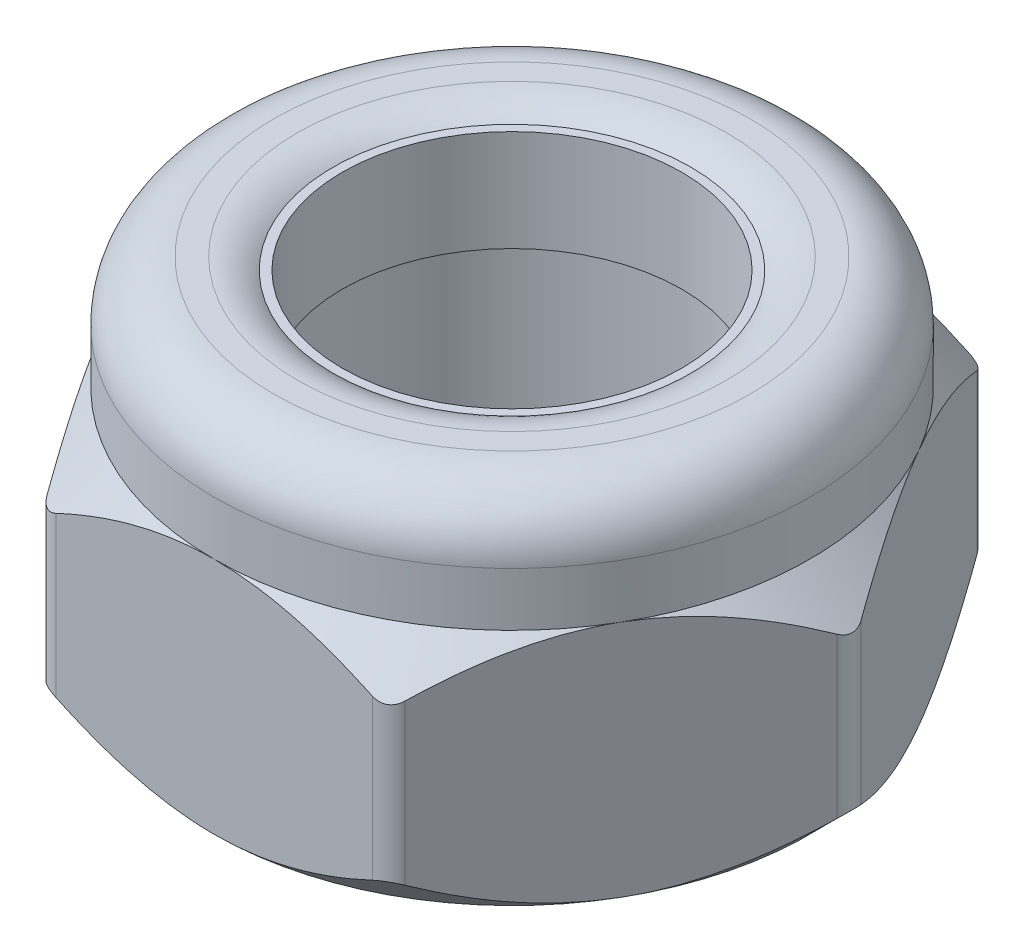
SolidWorks part; units mm, degrees
material "铸造碳钢"
ref_plane "Front" through (0, 0, 0) normal (0, 0, 1) x (1, 0, 0)
ref_plane "Top" through (0, 0, 0) normal (0, 1, 0) x (1, 0, 0)
ref_plane "Right" through (0, 0, 0) normal (1, 0, 0) x (0, 0, -1)
sketch "草图1" plane through (0, 0, 0) normal (0, 1, 0) x (1, 0, 0)
  line L1 (5.7735, 0) -> (2.8868, 5)
  line L2 (2.8868, 5) -> (-2.8868, 5)
  line L3 (-2.8868, 5) -> (-5.7735, 0)
  line L4 (-5.7735, 0) -> (-2.8868, -5)
  line L5 (-2.8868, -5) -> (2.8868, -5)
  line L6 (2.8868, -5) -> (5.7735, 0)
  circle A0 centre (0, 0) radius 5 construction
  dimension "六角对边长" = 10
extrude "凸台-拉伸1" add sketch "草图1" along normal mid plane 4
sketch "草图3" plane through (0, 2, 0) normal (0, 1, 0) x (1, 0, 0)
  circle A0 centre (0, 0) radius 5
  dimension "圆形外直径" = 10
extrude "凸台-拉伸2" add sketch "草图3" along normal blind 1.9
sketch "草图4" plane through (0, 3.9, 0) normal (0, 1, 0) x (1, 0, 0)
  circle A0 centre (0, 0) radius 3
  dimension "螺母内径" = 6
extrude "切除-拉伸1" cut sketch "草图4" against normal through all
sketch "草图5" plane through (0, 3.9, 0) normal (0, 1, 0) x (1, 0, 0)
  circle A0 centre (0, 0) radius 3
  circle A1 centre (0, 0) radius 2.85
  dimension "橡胶内径" = 5.7
  dimension "橡皮圈外直径" = 6
extrude "凸台-拉伸3" add sketch "草图5" against normal up to surface (1.9 mm away) from offset 0.2 up to face at (-5.0345, 2, 0) offset against normal yes
fillet "圆角1" radius 1 2 edges at (0, 3.9, 3) (0, 3.9, 5)
sketch "草图6" plane through (0, 0, 0) normal (0, 0, 1) x (1, 0, 0)
  line L0 (0, -1000) -> (0, 49000) construction
  line L1 (-1000, 0) -> (49000, 0) construction
  line L2 (-5.7735, 2) -> (-5.7735, 1.2265)
  line L3 (-5.7735, 1.2265) -> (-5, 2)
  line L4 (-5, 2) -> (-5.7735, 2)
  line L5 (0, 2) -> (-4.3301, 2) construction
  line L6 (-5.7735, 2) -> (-5.7735, -2) construction
  line L7 (-5, -998.4247) -> (-5, 49001.5753) construction
  line L8 (-5, 2.9) -> (-5, 2) construction
  line L9 (-5.7735, -2) -> (-5.7735, -1.2265)
  line L10 (-5.7735, -1.2265) -> (-5, -2)
  line L11 (-5, -2) -> (-5.7735, -2)
  dimension "D1" = 45
revolve "切除-旋转1" cut sketch "草图6" angle 360 about L0
fillet "圆角3" radius 0.4 6 edges at (-5.7735, 0, 0) (-2.8868, 0, -5) (2.8868, 0, -5) (5.7735, 0, 0) (2.8868, 0, 5) (-2.8868, 0, 5)
other "冻结***"
move or copy body "Body-Move/Copy1" [suppressed] bodies to move or copy 105
move or copy body "Body-Move/Copy2" [suppressed] bodies to move or copy 105
